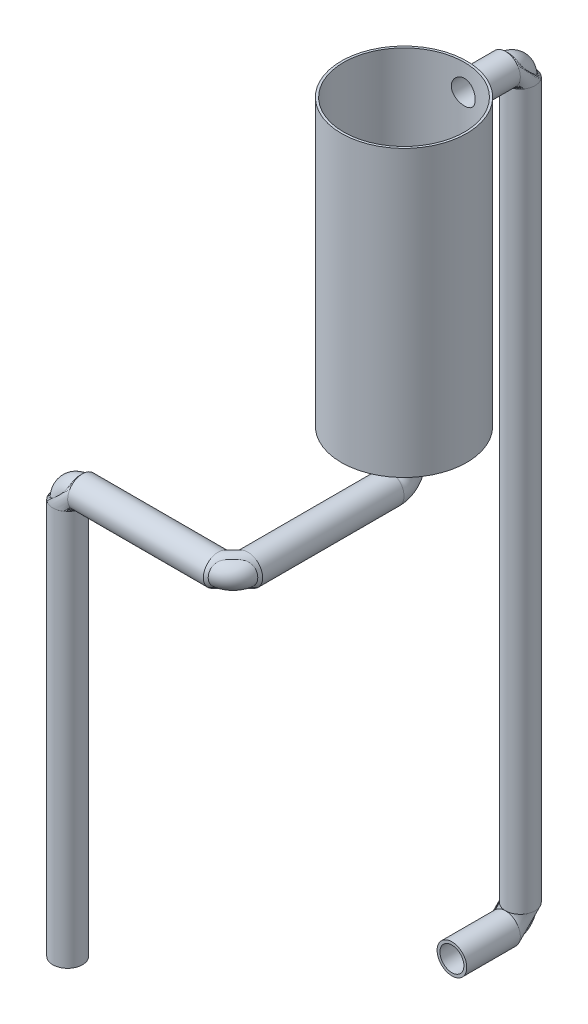
SolidWorks part; units mm, degrees
ref_plane "Front Plane" through (0, 0, 0) normal (0, 0, 1) x (1, 0, 0)
ref_plane "Top Plane" through (0, 0, 0) normal (0, 1, 0) x (1, 0, 0)
ref_plane "Right Plane" through (0, 0, 0) normal (1, 0, 0) x (0, 0, -1)
sketch "Sketch1" plane through (0, 0, 0) normal (0, 1, 0) x (1, 0, 0)
  circle A0 centre (0, 0) radius 55
  dimension "D1" = 110
extrude "Boss-Extrude1" add sketch "Sketch1" along normal blind 250
shell "Shell1" thickness 2 removed face at (0, 250, 55)
ref_plane "Plane1" through (0, 0, -75) normal (0, 0, 1) x (1, 0, 0)
sketch "Sketch3" plane through (0, 0, -75) normal (0, 0, 1) x (1, 0, 0)
  line L0 (53, 250) -> (-53, 250) construction
  point P0 (0, 250)
  point P1 (0, 0)
ref_plane "Plane2" through (-75, 0, 0) normal (1, 0, 0) x (0, 0, -1)
sketch "Sketch5" plane through (-75, 0, 0) normal (1, 0, 0) x (0, 0, -1)
  line L0 (-55, 0) -> (55, 0) construction
  circle A0 centre (0, 40) radius 13
  dimension "D1" = 26
  dimension "D2" = 0
  dimension "D3" = 40
extrude "Cut-Extrude1" [suppressed] cut sketch "Sketch5" along normal blind 43
sketch "Sketch6" plane through (0, 0, 0) normal (0, -1, 0) x (1, 0, 0)
  circle A0 centre (0, 0) radius 13
  dimension "D1" = 26
extrude "Cut-Extrude2" cut sketch "Sketch6" against normal blind 43
sketch "Sketch8" [suppressed] plane through (-75, 0, 0) normal (1, 0, 0) x (0, 0, -1)
  circle A0 centre (0, 40) radius 13
sketch "Sketch9" [suppressed] plane through (0, 0, 0) normal (0, 0, 1) x (1, 0, 0)
  line L0 (-75, 40) -> (-132, 40)
  line L1 (-75, 27) -> (-75, 53) construction
  line L2 (-145, 27) -> (-145, -352.47)
  line L3 (-132, -365.47) -> (-115, -365.47)
  arc A0 (-132, 40) -> (-145, 27) centre (-132, 27) ccw
  arc A1 (-145, -352.47) -> (-132, -365.47) centre (-132, -352.47) ccw
  point P8 (-145, 40)
  point P11 (-145, -365.47)
  dimension "D3" = 13
  dimension "D5" = 13
  dimension "D1" = 70
  dimension "D2" = 405.47
  dimension "D4" = 30
sketch "Sketch10" [suppressed] plane through (-75, 0, 0) normal (1, 0, 0) x (0, 0, -1)
  circle A0 centre (0, 40) radius 13 construction
  circle A1 centre (0, 40) radius 13
  circle A2 centre (0, 40) radius 11
  dimension "D1" = 2
sweep "Sweep2" [suppressed] add profiles "Sketch10" path "Sketch9"
sketch3d "3DSketch2"
  line L0 (0, 0, 0) -> (0, -27, 0)
  line L1 (0, -40, 13) -> (0, -40, 137)
  line L2 (-13, -40, 150) -> (-132, -40, 150)
  line L3 (-145, -53, 150) -> (-145, -400, 150)
  arc A0 (0, -27, 0) -> (0, -40, 13) centre (0, -27, 13) ccw
  arc A1 (0, -40, 137) -> (-13, -40, 150) centre (-13, -40, 137) ccw
  arc A2 (-132, -40, 150) -> (-145, -53, 150) centre (-132, -53, 150) ccw
  point P8 (0, -40, 0)
  point P9 (-13, -27, 13)
  point P12 (0, -40, 150)
  point P13 (-13, -53, 137)
  point P16 (-145, -40, 150)
  point P17 (-132, -53, 163)
  dimension "D1" = 13
  dimension "D2" = 360
  dimension "D3" = 40
  dimension "D4" = 150
  dimension "D5" = 145
sketch "Sketch16" plane through (0, 0, 0) normal (0, -1, 0) x (1, 0, 0)
  circle A0 centre (0, 0) radius 11
sketch "Sketch18" plane through (0, 0, 0) normal (0, -1, 0) x (1, 0, 0)
  circle A0 centre (0, 0) radius 13
  circle A1 centre (0, 0) radius 11
sweep "Sweep6" add profiles "Sketch18" path "3DSketch2"
ref_plane "Plane3" through (0, 0, -72) normal (0, 0, 1) x (1, 0, 0)
sketch "Sketch19" plane through (0, 0, -72) normal (0, 0, 1) x (1, 0, 0)
  circle A0 centre (0, 227.3193) radius 13
  dimension "D1" = 26
extrude "Cut-Extrude3" cut sketch "Sketch19" against normal blind 30 and the other way blind 40
sketch "Sketch20" plane through (0, 0, -72) normal (0, 0, 1) x (1, 0, 0)
  circle A0 centre (0, 227.3193) radius 13
  circle A1 centre (0, 227.3193) radius 10.5
  point P5 (0, 227.3193)
  dimension "D1" = 21
sketch3d "3DSketch4"
  line L0 (0, 227.3193, -72) -> (0, 227.3193, -89)
  line L1 (0, 214.3193, -102) -> (0, -412.4707, -102)
  line L2 (0, -425.4707, -89) -> (0, -425.4707, -42)
  arc A0 (0, -412.4707, -102) -> (0, -425.4707, -89) centre (0, -412.4707, -89) ccw
  arc A1 (0, 227.3193, -89) -> (0, 214.3193, -102) centre (0, 214.3193, -89) ccw
  point P6 (0, -425.4707, -102)
  point P7 (-13, -412.4707, -89)
  point P10 (0, 227.3193, -102)
  point P11 (-13, 214.3193, -89)
  dimension "D1" = 13
  dimension "D2" = 652.79
  dimension "D3" = 0
  dimension "D4" = 30
  dimension "D5" = 60
sweep "Sweep7" add profiles "Sketch20" path "3DSketch4"
ref_point "Point1"
sketch "Sketch21" plane through (0, 0, -72) normal (0, 0, 1) x (1, 0, 0)
  circle A0 centre (0, 227.3193) radius 10.5
  circle A1 centre (0, 227.3193) radius 13
extrude "Boss-Extrude2" add sketch "Sketch21" along normal blind 21
sketch "Sketch22" plane through (0, 250, 0) normal (0, 1, 0) x (1, 0, 0)
  line L0 (13, 51) -> (-13, 51)
  line L1 (-13, 51) -> (-13, 51.3809)
  line L2 (-13, 51.3809) -> (-13, 51) construction
  line L3 (13, 51) -> (13, 51.3809)
  circle A0 centre (0, 0) radius 53 construction
  arc A2 (13, 51.3809) -> (-13, 51.3809) centre (0, 0) ccw
  circle M1 centre (0, 0) radius 53
extrude "Cut-Extrude4" cut sketch "Sketch22" against normal blind 50 contours L0 L3 L1 M1 region at (0, 250, -51.8111)
